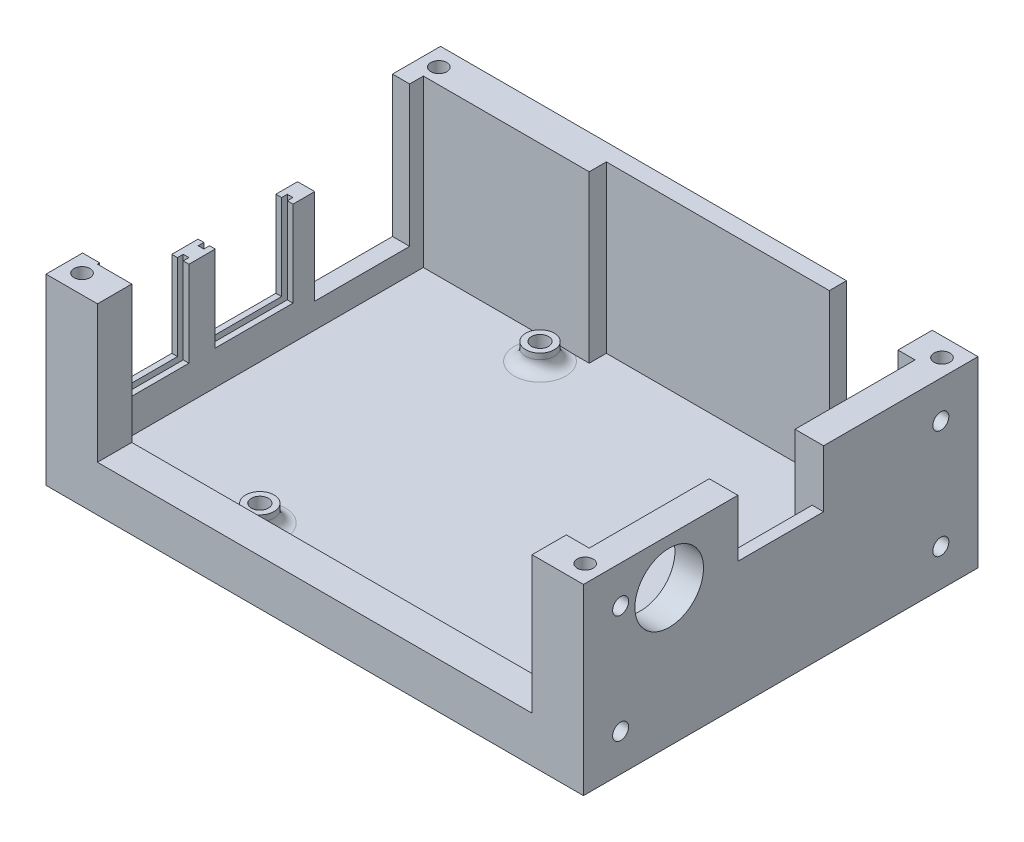
SolidWorks part; units mm, degrees
ref_plane "Front" through (0, 0, 0) normal (0, 0, 1) x (1, 0, 0)
ref_plane "Top" through (0, 0, 0) normal (0, 1, 0) x (1, 0, 0)
ref_plane "Right" through (0, 0, 0) normal (1, 0, 0) x (0, 0, -1)
sketch "Sketch1" plane through (0, 0, 0) normal (0, 1, 0) x (1, 0, 0)
  line L0 (-47, 34.5) -> (47, -34.5) construction
  line L1 (-47, 34.5) -> (47, 34.5)
  line L2 (-47, 34.5) -> (-47, -34.5)
  line L3 (-47, -34.5) -> (47, -34.5)
  line L4 (47, 34.5) -> (47, -34.5)
  point P4 (0, 0)
  point P5 (0, 0)
  point P7 (63.8263, -23.6)
  point P8 (0, 0)
  dimension "D1" = 69
  dimension "D2" = 94
extrude "pi_base" add sketch "Sketch1" along normal blind 3
sketch "Sketch2" plane through (0, 3, 0) normal (0, 1, 0) x (1, 0, 0)
  line L0 (-44, 28.5) -> (-44, -28.5)
  line L1 (-47, 34.5) -> (47, 34.5)
  line L2 (-47, 34.5) -> (-47, -34.5)
  line L3 (-47, -34.5) -> (47, -34.5)
  line L4 (47, 34.5) -> (47, -34.5)
  line L5 (-44, -28.5) -> (42, -28.5)
  line L6 (42, 28.5) -> (42, -28.5)
  line L7 (-44, 28.5) -> (42, 28.5)
  point P10 (43, -28)
  point P11 (43, 29)
  dimension "D1" = 6
  dimension "D2" = 3
  dimension "D3" = 86
  dimension "D4" = 57
extrude "pi_walls" add sketch "Sketch2" along normal blind 29
sketch "Sketch3" plane through (-47, 0, 0) normal (-1, 0, 0) x (0, 0, 1)
  line L0 (-34.5, 32) -> (34.5, 32) construction
  line L1 (-26.1, 32) -> (-9.5, 32)
  line L2 (-26.1, 32) -> (-26.1, 7.4)
  line L3 (-26.1, 7.4) -> (-9.5, 7.4)
  line L4 (-9.5, 32) -> (-9.5, 7.4)
  line L5 (-28.5, 32) -> (-28.5, 0) construction
  line L6 (-5.7, 32) -> (7.9, 32)
  line L7 (-5.7, 32) -> (-5.7, 9)
  line L8 (-5.7, 9) -> (7.9, 9)
  line L9 (7.9, 32) -> (7.9, 9)
  line L10 (12.5, 32) -> (26.1, 32)
  line L11 (12.5, 32) -> (12.5, 9)
  line L12 (12.5, 9) -> (26.1, 9)
  line L13 (26.1, 32) -> (26.1, 9)
  line L14 (-34.5, 0) -> (34.5, 0) construction
  line L16 (28.5, 32) -> (28.5, 0) construction
  line L18 (-28.5, 6) -> (28.5, 6) construction
  line L19 (-28.5, 32) -> (-28.5, 3) construction
  line L20 (28.5, 32) -> (28.5, 3) construction
  point P27 (-26.1, 19.7)
  line M18 (34.5, 32) -> (-34.5, 32)
  dimension "D2" = 6
  dimension "D3" = 1.4
  dimension "D4" = 16.6
  dimension "D5" = 13.6
  dimension "D6" = 3
  dimension "D8" = 3.8
  dimension "D9" = 4.6
  dimension "D10" = 2.4
sketch "Sketch4" plane through (0, 3, 0) normal (0, 1, 0) x (1, 0, 0)
  line L0 (42, 0) -> (38.4, 0) construction
  line L1 (-19.6, 24.5) -> (38.4, 24.5) construction
  line L2 (-19.6, 24.5) -> (-19.6, -24.5) construction
  line L3 (-19.6, -24.5) -> (38.4, -24.5) construction
  line L4 (38.4, 24.5) -> (38.4, -24.5) construction
  line L7 (42, -28.5) -> (42, 28.5) construction
  circle A0 centre (-19.6, 24.5) radius 2.5
  circle A1 centre (38.4, 24.5) radius 2.5
  circle A2 centre (-19.6, -24.5) radius 2.5
  circle A3 centre (38.4, -24.5) radius 2.5
  dimension "D1" = 5
  dimension "D2" = 3.6
  dimension "D3" = 49
  dimension "D4" = 58
extrude "stand_offs" add sketch "Sketch4" along normal blind 3 contours A0 | A1 | A3 | A2 region at (-19.6, 3, -24.5) region at (38.4, 3, -24.5) region at (-19.6, 3, 24.5) region at (38.4, 3, 24.5)
sketch "Sketch5" plane through (0, 0, -28.5) normal (0, 0, 1) x (1, 0, 0)
  line L0 (42, 32) -> (-44, 32) construction
  line L1 (-15, 32) -> (39, 32)
  line L2 (-15, 32) -> (-15, 3)
  line L3 (-15, 3) -> (39, 3)
  line L4 (39, 32) -> (39, 3)
  line L5 (-12, 32) -> (-12, 3) construction
  line L6 (42, 32) -> (42, 3) construction
  line L8 (42, 3) -> (-44, 3) construction
  dimension "D1" = 54
  dimension "D2" = 3
  dimension "D3" = 54
sketch "Sketch6" plane through (0, 6, 0) normal (0, 1, 0) x (1, 0, 0)
  line L1 (-19.6, 24.5) -> (38.4, 24.5) construction
  line L2 (-19.6, 24.5) -> (-19.6, -24.5) construction
  line L3 (-19.6, -24.5) -> (38.4, -24.5) construction
  line L4 (38.4, 24.5) -> (38.4, -24.5) construction
  circle A0 centre (-19.6, 24.5) radius 1.5
  circle A1 centre (38.4, 24.5) radius 1.5
  circle A2 centre (-19.6, -24.5) radius 1.5
  circle A3 centre (38.4, -24.5) radius 1.5
  circle A4 centre (38.4, -24.5) radius 2.5 construction
  circle A5 centre (-19.6, -24.5) radius 2.5 construction
  circle A6 centre (38.4, 24.5) radius 2.5 construction
  circle A7 centre (-19.6, 24.5) radius 2.5 construction
  circle A8 centre (38.4, -24.5) radius 2.5 construction
  circle A9 centre (-19.6, -24.5) radius 2.5 construction
  circle A10 centre (38.4, 24.5) radius 2.5 construction
  circle A11 centre (-19.6, 24.5) radius 2.5 construction
  dimension "D1" = 3
extrude "pi_mount_holes" cut sketch "Sketch6" against normal up to surface (6 mm away) up to face at (0, 0, 0)
fillet "standoff_fillet" radius 2 4 edges at (38.4, 3, -22) (-19.6, 3, -22) (-19.6, 3, 27) (38.4, 3, 27)
extrude "hdmi_aux_cut" cut sketch "Sketch5" against normal blind 3
sketch "Sketch10" plane through (0, 0, -31.5) normal (0, 0, 1) x (1, 0, 0)
  line L0 (39, 32) -> (-15, 32) construction
  line L1 (39, 3) -> (24, 3)
  line L2 (39, 3) -> (39, 32)
  line L3 (39, 32) -> (24, 32)
  line L4 (24, 3) -> (24, 32)
  point P5 (24.5, 23)
  dimension "D1" = 15
extrude "pwr_cut_through" cut sketch "Sketch10" against normal up to surface (3 mm away) up to face at (0, 16, -34.5)
extrude "eth_usb_cut" cut sketch "Sketch3" against normal blind 3 contours L4 L2 L3 M18 | L9 L7 L8 M18 | L13 L11 L12 M18 region at (-47, 20.5, 19.3) region at (-47, 20.5, 1.1) region at (-47, 19.7, -17.8)
sketch "Sketch8" plane through (0, 32, 0) normal (0, 1, 0) x (1, 0, 0)
  line L0 (-45.5, 9.5) -> (-45.5, 6.7) construction
  line L1 (-46, 6.7) -> (-45, 6.7)
  line L2 (-46, 6.7) -> (-46, -8.9)
  line L3 (-46, -27.1) -> (-45, -27.1)
  line L4 (-45, 6.7) -> (-45, -8.9)
  line L5 (-44, 9.5) -> (-47, 9.5) construction
  line L6 (-44, 5.7) -> (-47, 5.7) construction
  line L7 (-44, -26.1) -> (-47, -26.1) construction
  line L8 (-45, -8.9) -> (-46, -8.9)
  line L9 (-46, -11.5) -> (-45, -11.5)
  line L10 (-44, -7.9) -> (-47, -7.9) construction
  line L11 (-44, -12.5) -> (-47, -12.5) construction
  line L12 (-46, -11.5) -> (-46, -27.1)
  line L13 (-45, -11.5) -> (-45, -27.1)
  dimension "D1" = 1
  dimension "D2" = 1
  dimension "D3" = 1
  dimension "D4" = 1
  dimension "D5" = 1
extrude "usb_flange_cut" cut sketch "Sketch8" against normal offset from surface (24 mm away) 1 up to face at (-45.5, 9, 1.1) offset beyond the face yes
sketch "Sketch16" plane through (42, 0, 0) normal (-1, 0, 0) x (0, 0, 1)
  line L0 (28.5, 32) -> (-28.5, 32) construction
  line L1 (-7.5, 32) -> (7.5, 32)
  line L2 (-7.5, 32) -> (-7.5, 5)
  line L3 (-7.5, 5) -> (7.5, 5)
  line L4 (7.5, 32) -> (7.5, 5)
  line L5 (0, 0) -> (0, 5) construction
  line L6 (28.5, 3) -> (27.2, 3) construction
  dimension "D1" = 15
  dimension "D2" = 2
extrude "sd_cut" cut sketch "Sketch16" against normal blind 3
sketch "Sketch12" plane through (47, 0, 0) normal (1, 0, 0) x (0, 0, -1)
  line L0 (0, 0) -> (0, 32) construction
  line L1 (-28, 25.5) -> (28, 25.5) construction
  line L2 (-28, 25.5) -> (-28, 6.5) construction
  line L3 (-28, 6.5) -> (28, 6.5) construction
  line L4 (28, 25.5) -> (28, 6.5) construction
  line L5 (-34.5, 32) -> (34.5, 32) construction
  line L6 (28, 16) -> (-28, 16) construction
  circle A0 centre (-28, 25.5) radius 1.4
  circle A1 centre (-28, 6.5) radius 1.4
  circle A2 centre (28, 6.5) radius 1.4
  circle A3 centre (28, 25.5) radius 1.4
  point P13 (0, 25.5)
  point P16 (0, 16)
  dimension "D1" = 2.8
  dimension "D2" = 19
  dimension "D3" = 56
extrude "pca_mounting_cut" cut sketch "Sketch12" against normal blind 4.4
sketch "Sketch13" plane through (42, 0, 0) normal (-1, 0, 0) x (0, 0, 1)
  line L3 (34.5, 32) -> (-34.5, 32) construction
  line L4 (34.5, 32) -> (34.5, 0) construction
  circle A0 centre (19.5, 24) radius 6
  point P2 (-17.8169, 17.4488)
  point P3 (0, 0)
  dimension "D1" = 12
  dimension "D2" = 15
  dimension "D3" = 8
extrude "cap_wire_hole" cut sketch "Sketch13" against normal up to surface (5 mm away) contours A0 up to face at (47, 25.5, -29.4)
sketch "Sketch15" plane through (0, 0, 34.5) normal (0, 0, 1) x (1, 0, 0)
  line L0 (-47, 32) -> (47, 32) construction
  line L1 (-38, 32) -> (38, 32)
  line L2 (-38, 32) -> (-38, 8)
  line L3 (-38, 8) -> (38, 8)
  line L4 (38, 32) -> (38, 8)
  line L5 (-47, 0) -> (47, 0) construction
  line L6 (-47, 32) -> (-47, 0) construction
  line L7 (47, 32) -> (47, 0) construction
  point P12 (47, 16)
  dimension "D1" = 8
  dimension "D2" = 9
  dimension "D3" = 9
extrude "side_panel_cut" cut sketch "Sketch15" against normal up to surface (6 mm away) up to face at (4.2, 10.2659, 28.5)
sketch "Sketch17" plane through (-47, 0, 0) normal (-1, 0, 0) x (0, 0, 1)
  line L0 (26.1, 32) -> (26.1, 9) construction
  line L1 (-9.5, 32) -> (28.1, 32)
  line L2 (-9.5, 32) -> (-9.5, 24)
  line L3 (-9.5, 24) -> (28.1, 24)
  line L4 (28.1, 32) -> (28.1, 24)
  line L6 (12.5, 9) -> (26.1, 9) construction
  dimension "D1" = 2
  dimension "D2" = 15
extrude "usb_top_trim" cut sketch "Sketch17" against normal up to surface (9 mm away) up to face at (-38, 20, 31.5)
sketch "Sketch18" plane through (0, 32, 0) normal (0, 1, 0) x (1, 0, 0)
  line L0 (44, -31.2) -> (-44, 31.2) construction
  line L1 (-44, 31.2) -> (44, 31.2) construction
  line L2 (-44, 31.2) -> (-44, -31.2) construction
  line L3 (-44, -31.2) -> (44, -31.2) construction
  line L4 (44, 31.2) -> (44, -31.2) construction
  circle A0 centre (-44, 31.2) radius 1.4
  circle A1 centre (44, 31.2) radius 1.4
  circle A2 centre (44, -31.2) radius 1.4
  circle A3 centre (-44, -31.2) radius 1.4
  dimension "D1" = 2.8
  dimension "D2" = 88
  dimension "D3" = 62.4
extrude "top_mounting_holes" cut sketch "Sketch18" against normal blind 5
sketch "Sketch19" plane through (45, 0, 0) normal (-1, 0, 0) x (0, 0, 1)
  line L0 (7.5, 5) -> (7.5, 32) construction
  line L1 (7.5, 22) -> (-7.5, 22)
  line L2 (7.5, 22) -> (7.5, 32)
  line L3 (7.5, 32) -> (-7.5, 32)
  line L4 (-7.5, 22) -> (-7.5, 32)
  point P4 (0, 0)
  dimension "D1" = 10
extrude "pca_power_cut" cut sketch "Sketch19" against normal up to next
